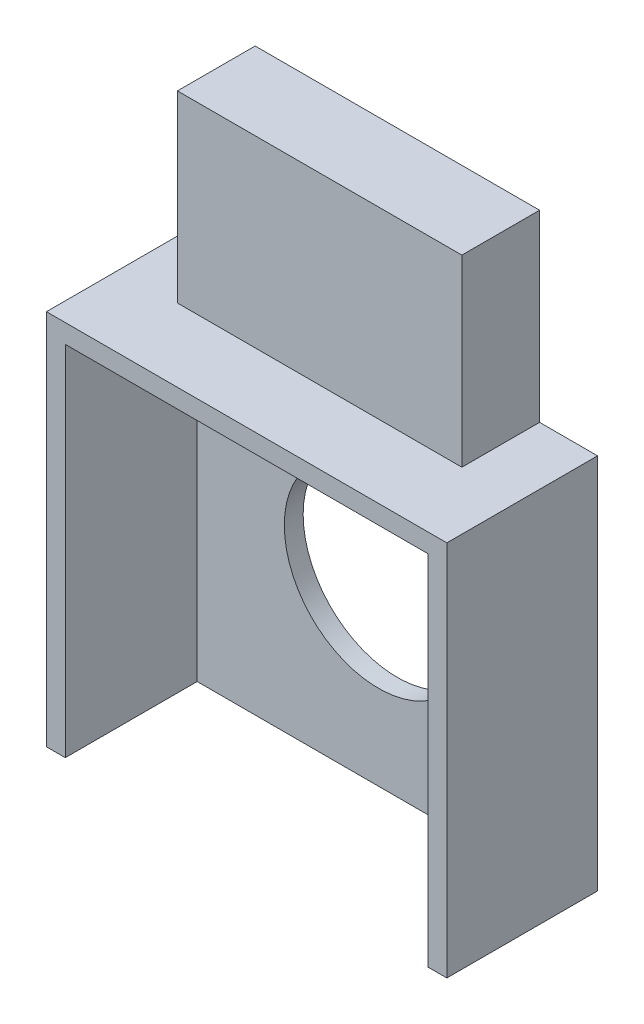
SolidWorks part; units mm, degrees
ref_plane "Front Plane" through (0, 0, 0) normal (0, 0, 1) x (1, 0, 0)
ref_plane "Top Plane" through (0, 0, 0) normal (0, 1, 0) x (1, 0, 0)
ref_plane "Right Plane" through (0, 0, 0) normal (1, 0, 0) x (0, 0, -1)
sketch "Sketch1" plane through (0, 0, 0) normal (0, 0, 1) x (1, 0, 0)
  line L1 (-19.25, 19) -> (19.25, 19)
  line L2 (-19.25, 19) -> (-19.25, -19)
  line L3 (-19.25, -19) -> (19.25, -19)
  line L4 (19.25, 19) -> (19.25, -19)
  line L5 (-19.25, 19) -> (19.25, -19) construction
  line L6 (-19.25, -19) -> (19.25, 19) construction
  line L7 (-13.095, 38.5) -> (13.095, 38.5)
  line L8 (-13.095, 38.5) -> (-13.095, -38.5)
  line L9 (-13.095, -38.5) -> (13.095, -38.5)
  line L10 (13.095, 38.5) -> (13.095, -38.5)
  line L11 (-13.095, 38.5) -> (13.095, -38.5) construction
  line L12 (-13.095, -38.5) -> (13.095, 38.5) construction
  circle A0 centre (0, 0) radius 10
  point P0 (0, 0)
  dimension "D3" = 20
  dimension "D1" = 38.5
  dimension "D2" = 38
  dimension "D4" = 77
  dimension "D5" = 26.19
extrude "Boss-Extrude1" add sketch "Sketch1" along normal blind 2 contours L8 L1 L2 L3 | L10 L1 L8 L3 A0 | L1 L10 L3 L4 | L10 L7 L8 L1 region at (-16.1725, 0, 0) region at (0, 28.75, 0) region at (0, 18.5385, 0) region at (16.1725, 0, 0)
sketch "Sketch2" plane through (0, 0, 2) normal (0, 0, 1) x (1, 0, 0)
  line L0 (19.25, -19) -> (21.25, -19)
  line L1 (21.25, -19) -> (21.25, 21)
  line L2 (21.25, 21) -> (13.095, 21)
  line L3 (13.095, 38.5) -> (13.095, 19) construction
  line L4 (-13.095, 19) -> (13.095, 19)
  line L5 (13.095, 19) -> (19.25, 19) construction
  line L8 (0, 40.5) -> (0, -19) construction
  line L10 (-19.25, -19) -> (19.25, -19) construction
  line L11 (-19.25, -19) -> (-21.25, -19)
  line L12 (-21.25, -19) -> (-21.25, 21)
  line L13 (-21.25, 21) -> (-13.095, 21)
  line L14 (-13.095, 21) -> (13.095, 21)
  line L15 (-13.095, 21) -> (-13.095, 19)
  line L16 (13.095, 21) -> (13.095, 19)
  line L17 (13.095, 19) -> (13.1276, 19.0166)
  line L23 (-19.25, -19) -> (19.25, -19)
  line L24 (19.25, -19) -> (19.25, 19)
  line L25 (19.25, 19) -> (13.095, 19)
  line L26 (13.095, 19) -> (13.095, 38.5)
  line L27 (13.095, 38.5) -> (-13.095, 38.5)
  line L28 (-13.095, 38.5) -> (-13.095, 19)
  line L29 (-13.095, 19) -> (-19.25, 19)
  line L30 (-19.25, 19) -> (-19.25, -19)
  line L31 (-19.25, -19) -> (19.25, -19)
  line L32 (19.25, -19) -> (19.25, 19)
  line L33 (19.25, 19) -> (13.095, 19)
  line L35 (13.095, 38.5) -> (-13.095, 38.5)
  line L37 (-13.095, 19) -> (-19.25, 19)
  line L38 (-19.25, 19) -> (-19.25, -19)
  line M17 (19.25, -19) -> (19.25, 19)
  line M18 (19.25, 19) -> (13.095, 19)
  line M19 (13.095, 19) -> (13.095, 38.5)
  line M20 (13.095, 38.5) -> (-13.095, 38.5)
  line M21 (-13.095, 38.5) -> (-13.095, 19)
  line M22 (-13.095, 19) -> (-19.25, 19)
  line M23 (-19.25, 19) -> (-19.25, -19)
  dimension "D1" = 2
  dimension "D2" = 2
  dimension "D5" = 0
extrude "Boss-Extrude2" add sketch "Sketch2" along normal blind 14 and the other way up to surface (2 mm away) contours L8 L13 L12 L11 L35 M23 M22 M21 | L8 L0 L1 L2 M20 M19 M18 M17 region at (19.7062, 3.5337, 2) region at (-19.7062, 3.5337, 2) other way up to face at (0, 14.375, 0)
sketch "Sketch3" plane through (0, 0, 2) normal (0, 0, 1) x (1, 0, 0)
  line L0 (15.095, 21) -> (15.095, 40.5)
  line L1 (21.25, 21) -> (13.095, 21) construction
  line L2 (15.095, 40.5) -> (-15.095, 40.5)
  line L3 (13.095, 38.5) -> (13.095, 21) construction
  line L4 (-13.095, 38.5) -> (13.095, 38.5) construction
  line L5 (0, 40.5) -> (0, 21) construction
  line L6 (15.095, 21) -> (13.095, 21)
  line L7 (-15.095, 21) -> (-13.095, 21)
  line L8 (-15.095, 21) -> (-15.095, 40.5)
  line L17 (-19.25, -19) -> (19.25, -19)
  line L18 (19.25, -19) -> (19.25, 19)
  line L19 (19.25, 19) -> (13.095, 19)
  line L20 (13.095, 19) -> (13.095, 21)
  line L21 (13.095, 21) -> (13.095, 38.5)
  line L22 (13.095, 38.5) -> (-13.095, 38.5)
  line L23 (-13.095, 38.5) -> (-13.095, 21)
  line L24 (-13.095, 21) -> (-13.095, 19)
  line L25 (-13.095, 19) -> (-19.25, 19)
  line L26 (-19.25, 19) -> (-19.25, -19)
  line L27 (-19.25, -19) -> (19.25, -19)
  line L28 (19.25, -19) -> (19.25, 19)
  line L29 (19.25, 19) -> (13.095, 19)
  line L30 (13.095, 19) -> (13.095, 21)
  line L31 (13.095, 21) -> (13.095, 38.5)
  line L32 (13.095, 38.5) -> (-13.095, 38.5)
  line L33 (-13.095, 38.5) -> (-13.095, 21)
  line L34 (-13.095, 21) -> (-13.095, 19)
  line L35 (-13.095, 19) -> (-19.25, 19)
  line L36 (-19.25, 19) -> (-19.25, -19)
  line M19 (13.095, 21) -> (13.095, 38.5)
  line M20 (13.095, 38.5) -> (-13.095, 38.5)
  line M21 (-13.095, 38.5) -> (-13.095, 21)
  dimension "D1" = 2
  dimension "D2" = 2
  dimension "D3" = 0
extrude "Boss-Extrude4" add sketch "Sketch3" along normal blind 4.25 and the other way up to surface (2 mm away) contours L5 L2 L8 L7 L32 M21 | L2 L5 L6 L0 M20 M19 region at (14.095, 21.2466, 2) region at (-0.2466, 39.5, 2) other way up to face at (0, 15.375, 0)
sketch "Sketch4" plane through (0, 0, 6.25) normal (0, 0, 1) x (1, 0, 0)
  line L1 (-15.095, 40.5) -> (15.095, 40.5)
  line L2 (-15.095, 40.5) -> (-15.095, 21)
  line L3 (-15.095, 21) -> (15.095, 21)
  line L4 (15.095, 40.5) -> (15.095, 21)
extrude "Boss-Extrude5" add sketch "Sketch4" along normal blind 2
sketch "Sketch5" plane through (-13.095, 0, 0) normal (1, 0, 0) x (0, 0, -1)
  line L0 (-6.25, 21) -> (-6.25, 19)
  line L7 (-16, 19) -> (-2, 19)
  line L8 (-2, 19) -> (-2, 38.5)
  line L9 (-2, 38.5) -> (-6.25, 38.5)
  line L10 (-6.25, 38.5) -> (-6.25, 21)
  line L11 (-6.25, 21) -> (-8.25, 21)
  line L12 (-8.25, 21) -> (-16, 21)
  line L13 (-16, 21) -> (-16, 19)
  line L14 (-16, 19) -> (-2, 19)
  line L15 (-2, 19) -> (-2, 38.5)
  line L16 (-2, 38.5) -> (-6.25, 38.5)
  line L17 (-6.25, 38.5) -> (-6.25, 21)
  line L18 (-6.25, 21) -> (-8.25, 21)
  line L19 (-8.25, 21) -> (-16, 21)
  line L20 (-16, 21) -> (-16, 19)
  line M8 (-16, 19) -> (-2, 19)
  line M12 (-6.25, 21) -> (-8.25, 21)
  line M13 (-8.25, 21) -> (-16, 21)
  line M14 (-16, 21) -> (-16, 19)
  dimension "D1" = 0
extrude "Boss-Extrude6" add sketch "Sketch5" along normal up to surface (26.19 mm away) contours L0 M12 M13 M14 M8 region at (-13.095, 20, 11.125) up to face at (13.095, 25.4286, 8.1071)
